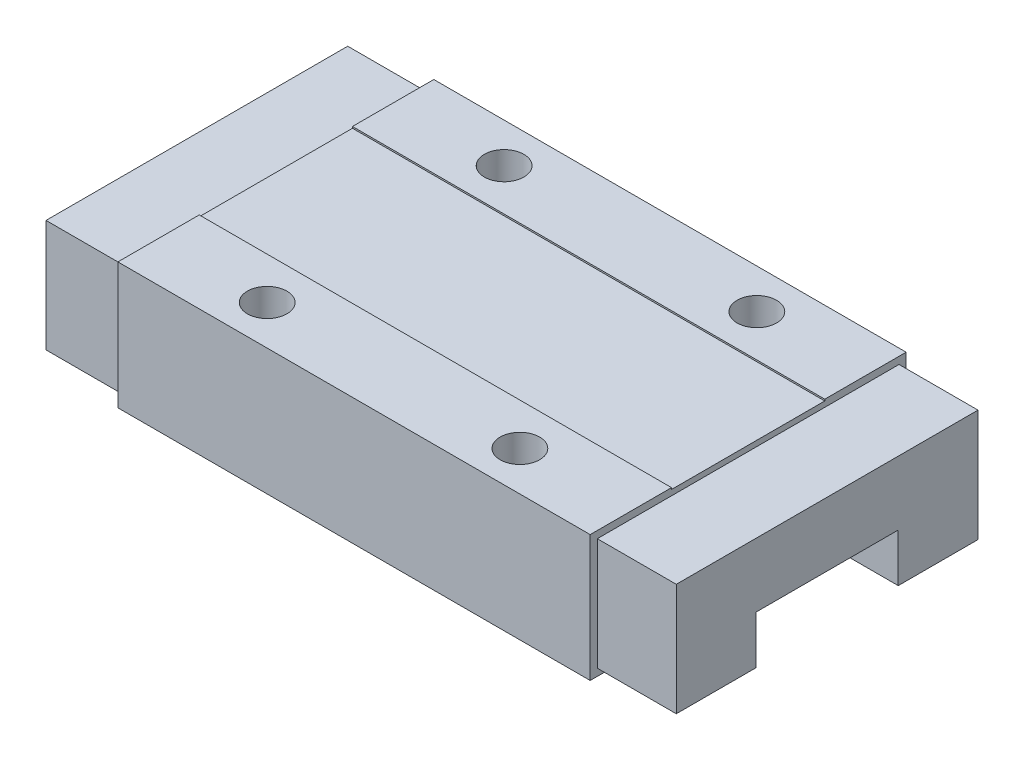
SolidWorks part; units mm, degrees
ref_plane "前视基准面" through (0, 0, 0) normal (0, 0, 1) x (1, 0, 0)
ref_plane "上视基准面" through (0, 0, 0) normal (0, 1, 0) x (1, 0, 0)
ref_plane "右视基准面" through (0, 0, 0) normal (1, 0, 0) x (0, 0, -1)
sketch "草图1" plane through (0, 0, 0) normal (1, 0, 0) x (0, 0, -1)
  line L1 (-10, 4) -> (10, 4)
  line L2 (-10, 4) -> (-10, -4)
  line L3 (-10, -4) -> (10, -4)
  line L4 (10, 4) -> (10, -4)
  line L5 (-10, 4) -> (10, -4) construction
  line L6 (-10, -4) -> (10, 4) construction
  point P0 (0, 0)
  dimension "D1" = 8
  dimension "D2" = 20
extrude "凸台-拉伸1" add sketch "草图1" along normal mid plane 29.9
sketch "草图2" plane through (0, 0, 0) normal (1, 0, 0) x (0, 0, -1)
  line L0 (10, 4) -> (-10, 4) construction
  line L1 (-4.85, 4.1) -> (4.85, 4.1)
  line L2 (-4.85, 4.1) -> (-4.85, 3.9)
  line L3 (-4.85, 3.9) -> (4.85, 3.9)
  line L4 (4.85, 4.1) -> (4.85, 3.9)
  line L5 (-4.85, 4.1) -> (4.85, 3.9) construction
  line L6 (-4.85, 3.9) -> (4.85, 4.1) construction
  point P0 (0, 4)
  dimension "D1" = 0.2
  dimension "D2" = 9.7
extrude "切除-拉伸1" cut sketch "草图2" against normal mid plane 29.9
sketch "草图3" plane through (0, 0, 0) normal (1, 0, 0) x (0, 0, -1)
  line L1 (-9.55, 3.55) -> (9.55, 3.55)
  line L2 (-9.55, 3.55) -> (-9.55, -3.55)
  line L3 (-9.55, -3.55) -> (9.55, -3.55)
  line L4 (9.55, 3.55) -> (9.55, -3.55)
  line L5 (-9.55, 3.55) -> (9.55, -3.55) construction
  line L6 (-9.55, -3.55) -> (9.55, 3.55) construction
  point P0 (0, 0)
  dimension "D1" = 7.1
  dimension "D2" = 19.1
extrude "凸台-拉伸2" add sketch "草图3" along normal mid plane 39.9
sketch "草图4" plane through (0, 0, 0) normal (1, 0, 0) x (0, 0, -1)
  line L0 (-10, -4) -> (10, -4) construction
  line L1 (-4.5, -4) -> (4.5, -4)
  line L2 (-4.5, -4) -> (-4.5, -0.5)
  line L3 (-4.5, -0.5) -> (4.5, -0.5)
  line L4 (4.5, -4) -> (4.5, -0.5)
  dimension "D1" = 3.5
  dimension "D2" = 9
  dimension "D3" = 4.5
extrude "切除-拉伸2" cut sketch "草图4" against normal mid plane 39.9
sketch "草图5" plane through (0, 4, 0) normal (0, 1, 0) x (1, 0, 0)
  line L1 (-8, 7.5) -> (8, 7.5) construction
  line L2 (-8, 7.5) -> (-8, -7.5) construction
  line L3 (-8, -7.5) -> (8, -7.5) construction
  line L4 (8, 7.5) -> (8, -7.5) construction
  line L5 (-8, 7.5) -> (8, -7.5) construction
  line L6 (-8, -7.5) -> (8, 7.5) construction
  circle A0 centre (-8, 7.5) radius 1.25
  circle A1 centre (8, 7.5) radius 1.25
  circle A2 centre (8, -7.5) radius 1.25
  circle A3 centre (-8, -7.5) radius 1.25
  point P0 (0, 0)
  dimension "D3" = 2.5
  dimension "D4" = 2.5
  dimension "D5" = 2.5
  dimension "D6" = 2.5
  dimension "D1" = 15
  dimension "D2" = 16
extrude "切除-拉伸3" cut sketch "草图5" against normal blind 3
cosmetic thread "装饰螺纹线1" parameters "D2"=3
cosmetic thread "装饰螺纹线2" parameters "D2"=3
cosmetic thread "装饰螺纹线3" parameters "D2"=3
cosmetic thread "装饰螺纹线4" parameters "D2"=3
